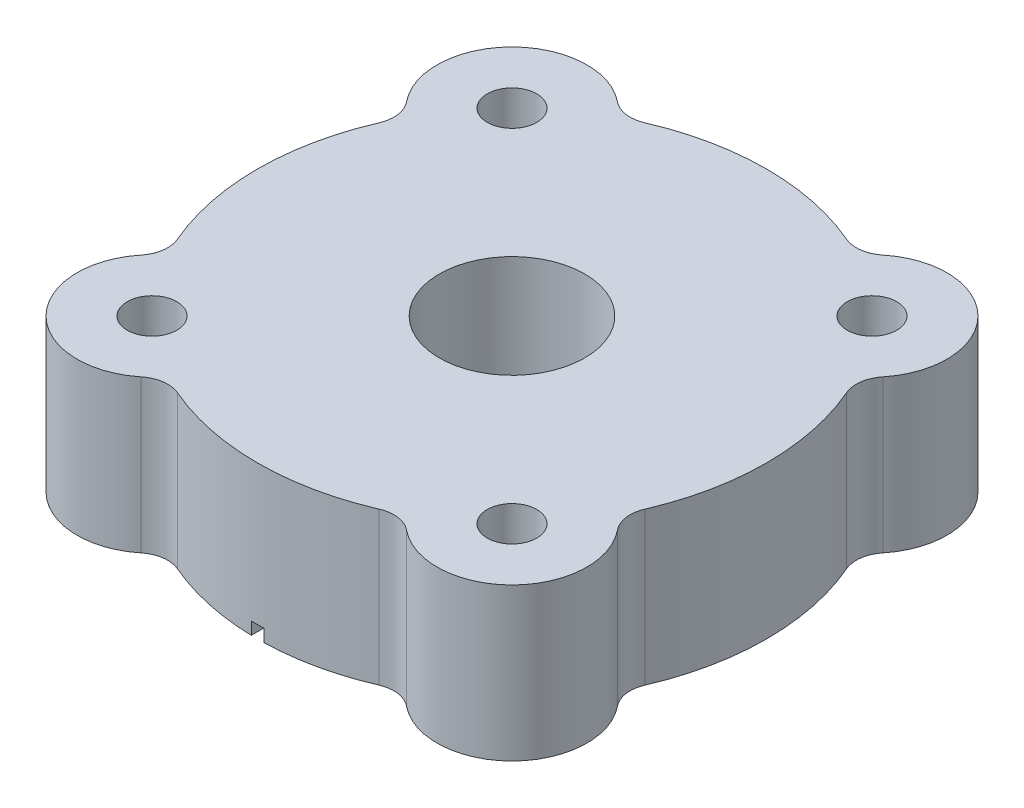
SolidWorks part; units mm, degrees
material "1060 Alloy"
ref_plane "Front" through (0, 0, 0) normal (0, 0, 1) x (1, 0, 0)
ref_plane "Top" through (0, 0, 0) normal (0, 1, 0) x (1, 0, 0)
ref_plane "Right" through (0, 0, 0) normal (1, 0, 0) x (0, 0, -1)
sketch "Sketch1" plane through (0, 0, 0) normal (0, 1, 0) x (1, 0, 0)
  line L0 (0, 0) -> (0, 40.75) construction
  circle A0 centre (-28.8146, 28.8146) radius 3.9688
  circle A1 centre (28.8146, 28.8146) radius 3.9687
  circle A2 centre (28.8146, -28.8146) radius 3.9687
  circle A3 centre (-28.8146, -28.8146) radius 3.9688
  circle A4 centre (0, 0) radius 10.1459
  arc A5 (-21.2538, 38.1331) -> (-38.1331, 21.2538) centre (-28.8146, 28.8146) ccw
  arc A6 (38.1331, 21.2538) -> (21.2538, 38.1331) centre (28.8146, 28.8146) ccw
  arc A7 (21.2538, -38.1331) -> (38.1331, -21.2538) centre (28.8146, -28.8146) ccw
  arc A8 (-38.1331, -21.2538) -> (-21.2538, -38.1331) centre (-28.8146, -28.8146) ccw
  arc A9 (-37.4239, 16.1249) -> (-37.4239, -16.1249) centre (0, 0) ccw
  arc A10 (-16.1249, -37.4239) -> (16.1249, -37.4239) centre (0, 0) ccw
  arc A11 (37.4239, -16.1249) -> (37.4239, 16.1249) centre (0, 0) ccw
  arc A12 (-16.1249, 37.4239) -> (-21.2538, 38.1331) centre (-18.1035, 42.0158) cw
  arc A13 (16.1249, 37.4239) -> (-16.1249, 37.4239) centre (0, 0) ccw
  arc A14 (21.2538, 38.1331) -> (16.1249, 37.4239) centre (18.1035, 42.0158) cw
  arc A15 (38.1331, 21.2538) -> (37.4239, 16.1249) centre (42.0158, 18.1035) ccw
  arc A16 (37.4239, -16.1249) -> (38.1331, -21.2538) centre (42.0158, -18.1035) ccw
  arc A17 (21.2538, -38.1331) -> (16.1249, -37.4239) centre (18.1035, -42.0158) ccw
  arc A18 (-16.1249, -37.4239) -> (-21.2538, -38.1331) centre (-18.1035, -42.0158) ccw
  arc A19 (-37.4239, -16.1249) -> (-38.1331, -21.2538) centre (-42.0158, -18.1035) cw
  arc A20 (-37.4239, 16.1249) -> (-38.1331, 21.2538) centre (-42.0158, 18.1035) ccw
  point P0 (0, 0)
  point P17 (0, 0)
  point P27 (0, 0)
  dimension "D5" = 7.9375
  dimension "D6" = 20.2918
  dimension "D1" = 5
  dimension "D2" = 12
  dimension "D3" = 40.75
  dimension "D4" = 4
  dimension "D8" = 4
extrude "body and main holes" add sketch "Sketch1" along normal blind 24.4122
sketch "Sketch3" plane through (0, 24.4122, 0) normal (0, -1, 0) x (1, 0, 0)
  circle A0 centre (0, 0) radius 11.6459
  dimension "D1" = 23.2918
extrude "seal bore" cut sketch "Sketch3" along normal blind 22.4122
sketch "Sketch4" plane through (0, 0, 0) normal (0, -1, 0) x (1, 0, 0)
  line L0 (0, 0) -> (0, 40.75) construction
  line L2 (-1, 40.75) -> (1, 40.75)
  line L3 (-1, 40.75) -> (-1, -40.75)
  line L4 (-1, -40.75) -> (1, -40.75)
  line L5 (1, 40.75) -> (1, -40.75)
  line L6 (-1, 40.75) -> (1, -40.75) construction
  line L7 (-1, -40.75) -> (1, 40.75) construction
  arc A0 (16.1249, 37.4239) -> (-16.1249, 37.4239) centre (0, 0) ccw construction
  arc A1 (-16.1249, -37.4239) -> (16.1249, -37.4239) centre (0, 0) ccw construction
  point P6 (0, 0)
  dimension "D1" = 2
extrude "vent slot" cut sketch "Sketch4" against normal blind 2
equation "\"D3@Sketch1\"=\"square plate bolt pattern diameter\"/2"
equation "\"D1@body and main holes\" = \"lower seal plate thickness\""
equation "\"D1@Sketch3\" = \"lower seal OD\""
equation "\"D1@seal bore\" = \"lower seal bore\""
equation "\"D5@Sketch1\"=\"m8 clearance\""
equation "\"D6@Sketch1\" = \"lower seal plate lip ID\""
equation "\"square plate bolt pattern diameter\"= \"motor OD\" + \"square plate bolt head diameter\" + 4mm"
equation "\"square plate bolt bore\" = 8mm"
equation "\"square plate bolt head diameter\" = 13.5mm"
equation "\"motor OD\" = 64mm"
equation "\"D2@Sketch1\"=\"motor mount post radius\""
equation "\"m6 clearance\" = 0.234375in 'this is 15/64 bit = 5.95mm, could use 6mm bit, B bit for 6.04mm or 1/4 bit for 6.35mm"
equation "\"m6 tap\" = 5mm   '5mm is appropriate, could use 13/64 or #5,6,7"
equation "\"m6 head bore diameter\" = 11mm  "
equation "\"m6 head bore depth\" = 7mm 'actual is 6mm"
equation "\"m8 clearance\" = 0.3125in 'this is 5/16in for 7.93mm, could use 8mm, O,P, or 21/64"
equation "\"m8 tap\" = 0.265625in  'this is 17/64 for 6.746875mm"
equation "\"m8 head bore diameter\" = 14mm"
equation "\"m8 head bore depth\" = 9mm 'actual is 8mm"
equation "\"lower seal OD\" = .917in  'this is https://www.mcmaster.com/#9281k121/=174001b"
equation "\"lower seal ID\"= .375in"
equation "\"lower seal depth\" = .625in + .218in"
equation "\"lower seal bore\" = \"lower seal depth\" + 1mm"
equation "\"impeller upper clearance\"= .5mm"
equation "\"impeller bottom clearance\"= .5mm"
equation "\"impeller dowel diameter\" = 2mm"
equation "\"impeller shaft bore depth\" = 12mm"
equation "\"impeller shaft bore\" = 8mm"
equation "\"impeller dowel length\" = 2mm*2 + \"impeller shaft bore\""
equation "\"square plate bolt head depth\" = 8mm"
equation "\"lower seal plate lip depth\" = 2mm"
equation "\"lower seal plate lip ID\" = \"lower seal OD\" - 3mm"
equation "\"lower seal plate thickness\" = \"lower seal plate lip depth\" + \"lower seal bore\""
equation "\"shaft coupler section diameter\" = 8mm"
equation "\"shaft bearing stop length\" = 3mm"
equation "\"shaft lower seal section diameter\" = \"lower seal ID\""
equation "\"shaft lower seal section length\" = \"lower seal plate thickness\" + 1mm"
equation "\"shaft impeller section diameter\" = \"impeller shaft bore\""
equation "\"upper seal plate pressure tap diameter\" = .328125in  'this is 21/64 drill for a 1/8 ANPT tap"
equation "\"motor mount post radius\"= ( 3 * \"square plate bolt bore\" ) / 2"
